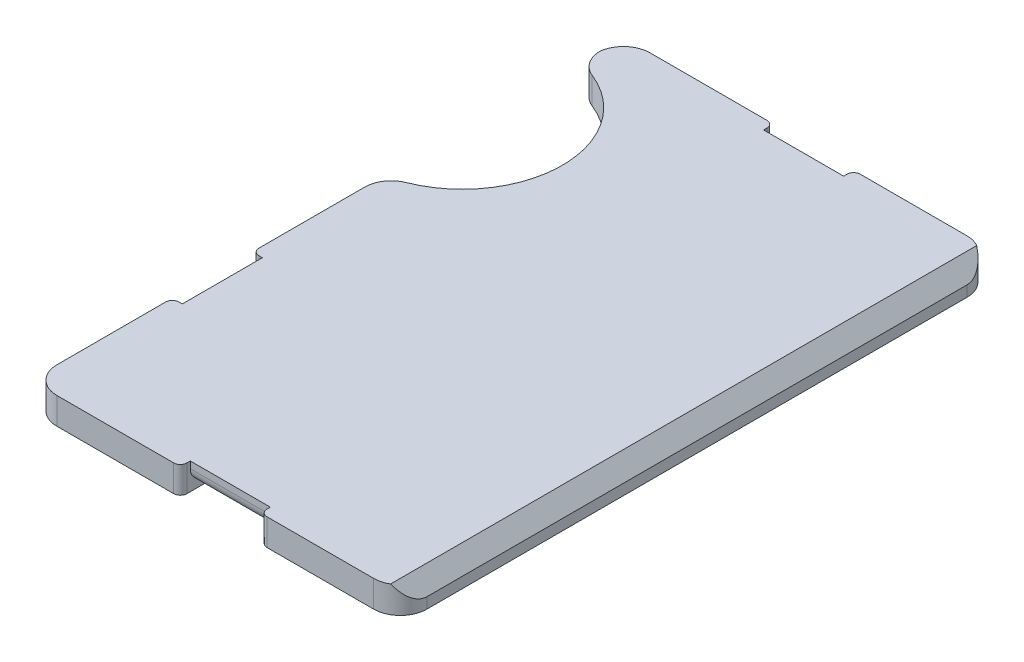
SolidWorks part; units mm, degrees
ref_plane "Front Plane" through (0, 0, 0) normal (0, 0, 1) x (1, 0, 0)
ref_plane "Top Plane" through (0, 0, 0) normal (0, 1, 0) x (1, 0, 0)
ref_plane "Right Plane" through (0, 0, 0) normal (1, 0, 0) x (0, 0, -1)
sketch "Sketch1" plane through (0, 0, 0) normal (0, 1, 0) x (1, 0, 0)
  line L0 (27, 44.5) -> (-28.5, 44.5)
  line L2 (27, -43) -> (-27, -43) construction
  line L4 (27, 43) -> (-27, 43) construction
  line L5 (-27, -43) -> (-27, 43) construction
  line L6 (27, -43) -> (-27, 43) construction
  line L7 (27, 43) -> (-27, -43) construction
  line L8 (27, -44.5) -> (-28.5, -44.5)
  line L9 (27, 44.5) -> (27, -44.5)
  line L10 (-6, 44.5) -> (-6, -44.5)
  line L11 (6, 44.5) -> (6, -44.5)
  line L12 (6, 4.3571) -> (27, 4.3571) construction
  line L13 (-6, 4.3571) -> (-27, 4.3571) construction
  line L15 (6, -11.1969) -> (-28.5, -11.1969)
  line L16 (6, -23.1969) -> (-28.5, -23.1969)
  line L17 (-28.5, 8.6061) -> (-28.5, -11.1969) construction
  line L18 (-28.5, -23.1969) -> (-28.5, -43) construction
  line L20 (-28.5, -44.5) -> (-28.5, 44.5) construction
  line L21 (-6, 43) -> (6, 43)
  line L23 (-6, -43) -> (6, -43)
  line L25 (-27, -11.1969) -> (-27, -23.1969)
  line L26 (-28.5, 44.5) -> (-28.5, -44.5)
  arc A0 (-28.5, 38) -> (-28.5, 8.6061) centre (-31.5, 23.3031) cw
  point P1 (0, 0)
  point P21 (6, -11.1969)
  point P22 (6, -23.1969)
  point P26 (-27, 4.3569)
  point P29 (-28.5, -11.1974)
  dimension "D4" = 15
  dimension "D1" = 86
  dimension "D2" = 54
  dimension "D5" = 3
  dimension "D6" = 12
  dimension "D10" = 12
  dimension "D11" = 5
  dimension "D3" = 1.5
extrude "Boss-Extrude1" add sketch "Sketch1" along normal blind 4 contours L26 A0 L15 L10 L0 | L21 L10 L15 L11 | L0 L11 L8 L9 | L16 L11 L15 L10 | L15 L25 L16 L10 | L16 L26 L8 L10 | L10 L23 L11 L16 region at (16.5, 0, 0) region at (-15.5858, 0, -14.876) region at (0, 0, -15.9015) region at (0, 0, 17.1969) region at (-17.25, 0, 33.8485) region at (0, 0, 33.0985) region at (-16.5, 0, 17.1969)
extrude "Cut-Extrude3" cut sketch "Sketch1<3>" along normal blind 1 contours L21 L10 L15 L11 | L10 L23 L11 L16 | L16 L11 L15 L10 | L15 L25 L16 L10 region at (0, 0, -15.9015) region at (0, 0, 17.1969) region at (0, 0, 33.0985) region at (-16.5, 0, 17.1969)
sketch "Sketch1<3>" plane through (0, 0, 0) normal (0, 1, 0) x (1, 0, 0) same geometry as "Sketch1"
extrude "Cut-Extrude4" cut sketch "Sketch1<4>" along normal blind 2 contours L16 L11 L15 L10 region at (0, 0, 17.1969)
sketch "Sketch1<4>" plane through (0, 0, 0) normal (0, 1, 0) x (1, 0, 0) same geometry as "Sketch1"
chamfer "Chamfer1" distance 2 angle 45 1 edges at (-6, 1, 17.1969)
fillet "Fillet2" radius 4 2 edges at (-28.5, 2, -8.6061) (-28.5, 2, -38)
chamfer "Chamfer2" distance 2 angle 50 1 edges at (27, 4, 0) first distance on face at (-10.7309, 4, -1.2212)
fillet "Fillet1" radius 4 4 edges at (-28.5, 2, 44.5) (-28.5, 2, -44.5) (27, 0.8082, -44.5) (27, 0.8082, 44.5)
fillet "Fillet3" radius 2 2 edges at (0, 1, 43) (0, 1, -43)
fillet "Fillet4" radius 1 6 edges at (-28.5, 2, 23.1969) (-28.5, 2, 11.1969) (-6, 2, -44.5) (6, 2, -44.5) (-6, 2, 44.5) (6, 2, 44.5)
sketch "Sketch3" plane through (0, 0, 0) normal (0, -1, 0) x (1, 0, 0)
  line L0 (26, 6.847) -> (26, -2.047)
  line L1 (26, -2.047) -> (22.5, -0.0263)
  line L2 (22.5, -0.0263) -> (22.5, 7.713)
  line L4 (22.5, 7.713) -> (18.5, 10.0224)
  line L5 (26, 6.847) -> (16.5, 12.3318)
  line L6 (18.5, 10.0224) -> (18.5, 2.2831)
  line L7 (18.5, 2.2831) -> (16.5, 3.4378)
  line L8 (16.5, 3.4378) -> (16.5, 12.3318)
  line L9 (6, 9.5) -> (27, -2.6244) construction
  line L10 (6, -43.5) -> (6, 43.5) construction
  line L11 (27, -40.5) -> (27, 40.5) construction
  line L12 (23, 44.5) -> (7, 44.5) construction
  line L13 (26, 39.3746) -> (26, 34.9748) construction
  line L14 (7, 8.8043) -> (7, 34.1656) construction
  line L15 (9, 7.7679) -> (9, 18.9713)
  line L16 (9, 18.9713) -> (26, 9.1564)
  line L17 (7, 8.9226) -> (7, 28.1651)
  line L18 (9, 22.4354) -> (26, 12.6205)
  line L19 (9, 22.4354) -> (9, 25.8557)
  line L20 (9, 25.8557) -> (13.8727, 23.0425)
  line L21 (13.8727, 23.0425) -> (13.8727, 33.0145)
  line L22 (7, 28.1651) -> (11.8727, 25.3519)
  line L23 (14.5, 4.5925) -> (11, 6.6132)
  line L24 (11, 6.6132) -> (11, 15.5072)
  line L25 (11, 15.5072) -> (14.5, 13.4865)
  line L26 (14.5, 13.4865) -> (14.5, 4.5925)
  line L27 (11.8727, 25.3519) -> (11.8727, 34.1692)
  line L28 (11.8727, 34.1692) -> (13.8727, 33.0145)
  line L29 (26, 19.0846) -> (21.241, 21.8322)
  line L30 (21.241, 21.8322) -> (21.241, 18.8322)
  line L31 (21.241, 18.8322) -> (26, 16.0846)
  line L32 (26, 16.0846) -> (26, 19.0846)
  line L33 (26, 12.6205) -> (26, 9.1564)
  line L34 (18.5, 26.8788) -> (18.5, 19.26)
  line L35 (18.5, 19.26) -> (16.5, 20.4147)
  line L36 (16.5, 20.4147) -> (16.5, 31.4976)
  line L37 (16.5, 31.4976) -> (26, 26.0128)
  line L38 (26, 26.0128) -> (26, 22.5487)
  line L39 (26, 22.5487) -> (18.5, 26.8788)
  line L40 (26, 34.0957) -> (26, 28.3222)
  line L41 (26, 28.3222) -> (9, 38.1371)
  line L42 (9, 38.1371) -> (9, 29.7425)
  line L43 (9, 29.7425) -> (7, 30.8972)
  line L44 (7, 30.8972) -> (7, 40.4465)
  line L45 (26, 34.0957) -> (15.8727, 39.9427)
  line L47 (22.5, 31.4976) -> (7, 40.4465)
  line L48 (22.5, 31.4976) -> (22.5, 34.9617)
  line L49 (22.5, 34.9617) -> (13.8727, 39.9427)
  line L50 (13.8727, 43.5) -> (13.8727, 39.9427)
  line L51 (15.8727, 39.9427) -> (15.8727, 43.5)
  line L52 (9.7013, 43.5) -> (20.5143, 43.5) construction
  line L53 (26, 36.4051) -> (18.8552, 40.5301)
  line L54 (18.8552, 40.5301) -> (18.8552, 43.5)
  line L55 (22.3552, 43.5) -> (22.3552, 39.6641)
  line L56 (22.3552, 39.6641) -> (26, 37.5598)
  line L57 (22.3552, 43.5) -> (18.8552, 43.5)
  line L58 (15.8727, 43.5) -> (13.8727, 43.5)
  line L59 (26, 37.5598) -> (26, 36.4051)
  line L60 (12.0384, 41.0017) -> (7.7113, 43.5)
  line L61 (12.0384, 41.0017) -> (12.0384, 43.5)
  line L66 (9, 7.7679) -> (7, 8.9226)
  line L67 (12.0384, 43.5) -> (7.7113, 43.5)
  point P68 (26, 15.9972)
  point P70 (12.1531, 41.7449)
  point P71 (16.201, 20.614)
  point P72 (13.3756, 13.6745)
  point P73 (16.5, 3.4378)
  point P74 (12.0384, 41.1809)
  point P75 (18.8552, 40.5301)
  dimension "D2" = 35
  dimension "D1" = 60
  dimension "D3" = 1
  dimension "D4" = 1
  dimension "D5" = 1
  dimension "D6" = 1
  dimension "D7" = 1
  dimension "D8" = 1
  dimension "D9" = 1
  dimension "D10" = 1
  dimension "D11" = 3
  dimension "D12" = 3
  dimension "D13" = 3
  dimension "D14" = 2
  dimension "D15" = 3.5
  dimension "D16" = 2
  dimension "D17" = 3.5
  dimension "D18" = 3.5
  dimension "D19" = 2
  dimension "D20" = 2
  dimension "D21" = 2
  dimension "D22" = 2
  dimension "D23" = 2
  dimension "D24" = 3
  dimension "D25" = 3
  dimension "D26" = 2
  dimension "D27" = 2
  dimension "D28" = 3.5
  dimension "D29" = 2
  dimension "D30" = 2
  dimension "D31" = 2
  dimension "D32" = 2
  dimension "D33" = 3
extrude "Cut-Extrude6" cut sketch "Sketch3" against normal blind 0.5
sketch "Sketch2" plane through (0, 0, 0) normal (0, -1, 0) x (1, 0, 0)
  line L0 (331.9721, 643.6489) -> (1611.9721, 643.6489) construction
  line L1 (11.7413, -19.4483) -> (17.887, -19.4483)
  line L2 (11.7413, -24.6483) -> (15.1413, -24.6483)
  line L3 (11.7413, -26.1483) -> (15.1413, -26.1483)
  line L4 (11.7413, -24.6483) -> (11.7413, -26.1483)
  line L5 (11.7413, -19.4483) -> (11.7413, -18.2483)
  line L6 (11.7413, -18.2483) -> (19.8591, -18.2483)
  line L7 (11.7413, -31.3483) -> (17.887, -31.3483)
  line L8 (11.7413, -31.3483) -> (11.7413, -32.5483)
  line L9 (11.7413, -32.5483) -> (19.8591, -32.5483)
  line L10 (21.2587, -19.5599) -> (21.2587, -31.2367) construction
  line L11 (20.0757, -19.3546) -> (20.0757, -31.4421) construction
  line L12 (20.5587, -20.5639) -> (20.5587, -30.2328) construction
  line L13 (21.2587, -19.5599) -> (21.2587, -31.2367)
  line L14 (20.5587, -22.4716) -> (20.5587, -28.325)
  line L15 (20.5587, -20.5639) -> (20.5587, -22.4716)
  line L16 (20.5587, -28.325) -> (20.5587, -30.2328)
  line L17 (11.7413, -31.3483) -> (6, -31.3483) construction
  line L18 (6, -43.5) -> (6, 43.5) construction
  line L19 (21.2587, -31.2367) -> (27, -31.2367) construction
  line L20 (27, -40.5) -> (27, 40.5) construction
  circle A0 centre (22.8587, -25.3983) radius 6.0537 construction
  circle A1 centre (22.8587, -25.3983) radius 6.6537 construction
  circle A2 centre (22.8587, -25.3983) radius 5.3537 construction
  circle A4 centre (22.8587, -25.3983) radius 7.7537 construction
  arc A5 (19.8591, -18.2483) -> (20.0757, -19.3546) centre (19.8332, -18.8277) cw
  arc A6 (19.8591, -32.5483) -> (20.0757, -31.4421) centre (19.8332, -31.9689) ccw
  arc A7 (17.887, -19.4483) -> (15.1413, -24.6483) centre (22.8587, -25.3983) ccw
  arc A8 (15.1413, -26.1483) -> (17.887, -31.3483) centre (22.8587, -25.3983) ccw
  arc A9 (20.0757, -19.3546) -> (20.0757, -31.4421) centre (22.8587, -25.3983) ccw
  arc A10 (21.2587, -19.5599) -> (21.2587, -31.2367) centre (22.8587, -25.3983) ccw
  arc A11 (20.5587, -20.5639) -> (20.5587, -30.2328) centre (22.8587, -25.3983) ccw
  circle A13 centre (22.1887, -25.3983) radius 3.35 construction
  arc A14 (20.5587, -22.4716) -> (20.5587, -28.325) centre (22.1887, -25.3983) ccw
  point P21 (11.7413, -25.3983)
  point P24 (19.8768, -27.8552)
  point P34 (0, 0)
  point P38 (0, 0)
  point P39 (0, 0)
  point P40 (0, 0)
  point P41 (27, -33.4228)
  point P46 (22.1887, -25.3983)
  dimension "D2" = 10.7074
  dimension "D3" = 0.7
  dimension "D4" = 0.6
  dimension "D5" = 1.1
  dimension "D12" = 0.58
  dimension "D13" = 0.58
  dimension "D15" = 0.7
  dimension "D16" = 6.7
  dimension "D6" = 1.5
  dimension "D7" = 5.2
  dimension "D8" = 5.2
  dimension "D9" = 1.2
  dimension "D10" = 1.2
  dimension "D11" = 1.6
  dimension "D14" = 3.4
  dimension "D17" = 0.67
extrude "Cut-Extrude5" cut sketch "Sketch2" against normal blind 0.5 contours L13 A10 A11 L15 L14 L16 | L14 A14 | A9 A5 L6 L5 L1 A7 L2 L4 L3 A8 L7 L8 L9 A6 region at (15.9731, 0, -25.3983) region at (21.1337, 0, -25.3983) region at (19.8528, 0, -25.3983)
